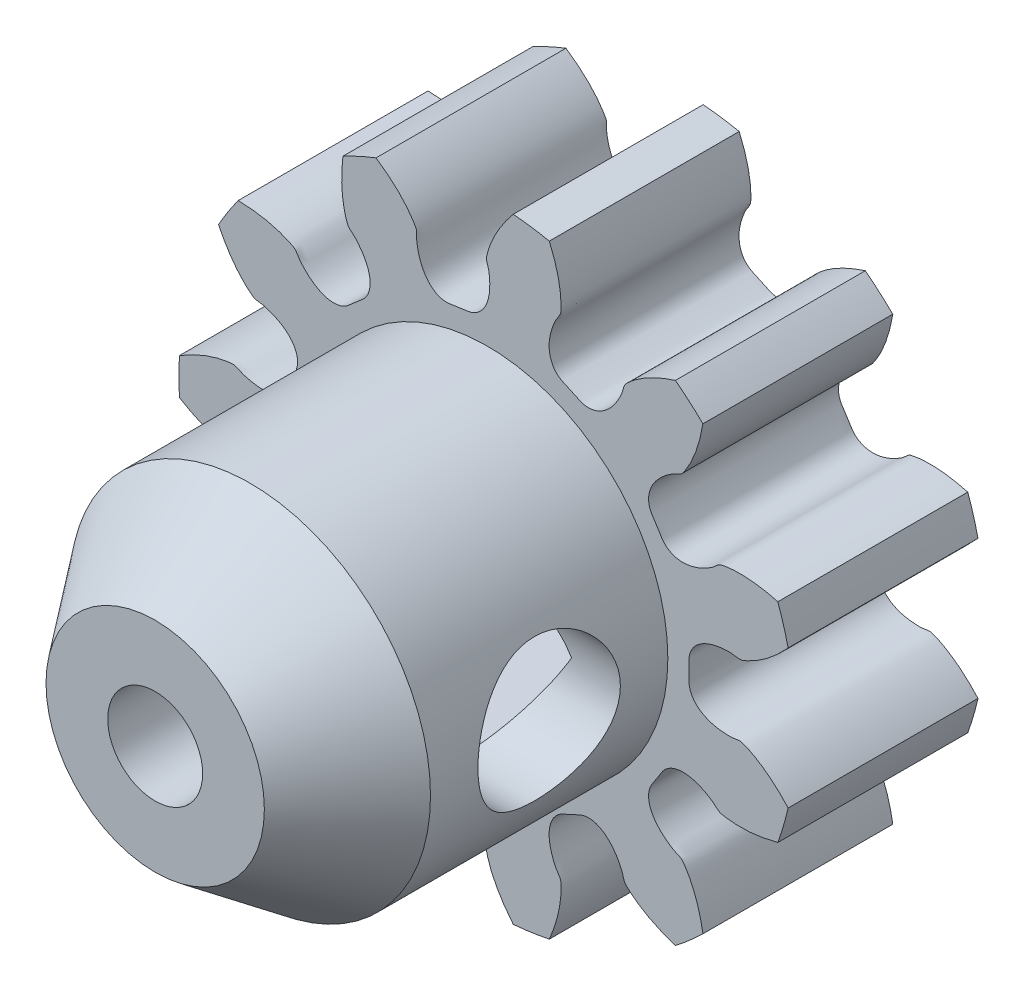
SolidWorks part; units mm, degrees
ref_plane "Front Plane" through (0, 0, 0) normal (0, 0, 1) x (1, 0, 0)
ref_plane "Top Plane" through (0, 0, 0) normal (0, 1, 0) x (1, 0, 0)
ref_plane "Right Plane" through (0, 0, 0) normal (1, 0, 0) x (0, 0, -1)
ref_axis "Axis1" through (0, 0, 55) along (0, 0, -1)
sketch "SketchRevolveSpurPinion" plane through (0, 0, 0) normal (1, 0, 0) x (0, 0, -1)
  line L0 (0, 0) -> (1, 0) construction
  line L1 (-2, 0) -> (-2, 6.5)
  line L2 (-2, 6.5) -> (2, 6.5)
  line L3 (2, 6.5) -> (2, 0)
  line L4 (2, 0) -> (-2, 0)
  dimension "Side1" = 2
  dimension "OutsideRadius" = 6.5
  dimension "Side2" = 2
revolve "SpurPinion" add sketch "SketchRevolveSpurPinion" angle 360 about L0
sketch "SketchToothSpurPinion" plane through (0, 0, 0) normal (0, 0, 1) x (1, 0, 0)
  arc A0 (6.3745, 1.5059) -> (6.3745, -1.5059) centre (0, 0) cw
  spline S0 degree 3 poles (6.3745, -1.5059) (6.3177, -1.4407) (6.2314, -1.3483) (6.113, -1.2348) (6.029, -1.1597) (5.9475, -1.092) (5.8691, -1.0315) (5.7941, -0.9778) (5.7229, -0.9306) (5.6559, -0.8896) (5.5935, -0.8543) (5.5358, -0.8245) (5.4834, -0.7993) (5.4233, -0.7745) (5.313, -0.7233) (5.1908, -0.7688) (5.0835, -0.7666) (5.0313, -0.7657) (4.9804, -0.7627) (4.9307, -0.7582) (4.8824, -0.7521) (4.8354, -0.7444) (4.7897, -0.7351) (4.7453, -0.7242) (4.7022, -0.7118) (4.6604, -0.6976) (4.6198, -0.6818) (4.5806, -0.6643) (4.5426, -0.6448) (4.506, -0.6234) (4.4707, -0.5999) (4.4368, -0.5741) (4.4045, -0.5458) (4.3739, -0.5148) (4.3453, -0.4808) (4.3191, -0.4436) (4.2958, -0.4032) (4.2761, -0.3595) (4.2606, -0.3128) (4.25, -0.2636) (4.2458, -0.218) (4.2449, -0.13) (4.2528, 0) (4.2449, 0.13) (4.2458, 0.218) (4.25, 0.2636) (4.2606, 0.3128) (4.2761, 0.3595) (4.2958, 0.4032) (4.3191, 0.4436) (4.3453, 0.4808) (4.3739, 0.5148) (4.4045, 0.5458) (4.4368, 0.5741) (4.4707, 0.5999) (4.506, 0.6234) (4.5426, 0.6448) (4.5806, 0.6643) (4.6198, 0.6818) (4.6604, 0.6976) (4.7022, 0.7118) (4.7453, 0.7242) (4.7897, 0.7351) (4.8354, 0.7444) (4.8824, 0.7521) (4.9307, 0.7582) (4.9804, 0.7627) (5.0313, 0.7657) (5.0835, 0.7666) (5.1908, 0.7688) (5.313, 0.7233) (5.4233, 0.7745) (5.4834, 0.7993) (5.5358, 0.8245) (5.5935, 0.8543) (5.6559, 0.8896) (5.7229, 0.9306) (5.7941, 0.9778) (5.8691, 1.0315) (5.9475, 1.092) (6.029, 1.1597) (6.113, 1.2348) (6.2314, 1.3483) (6.3177, 1.4407) (6.3745, 1.5059) knots 0 0 0 0 0.045121 0.0659 0.085492 0.103896 0.121113 0.137143 0.151985 0.16564 0.178107 0.189388 0.19948 0.208386 0.223471 0.261154 0.27045 0.279528 0.288392 0.297051 0.305514 0.313791 0.321893 0.329833 0.337626 0.345288 0.35284 0.360302 0.3677 0.375062 0.382419 0.389805 0.397257 0.404815 0.412518 0.420401 0.428492 0.43681 0.445354 0.454105 0.463019 0.469161 0.5 0.530839 0.536981 0.545895 0.554646 0.56319 0.571508 0.579599 0.587482 0.595185 0.602743 0.610195 0.617581 0.624938 0.6323 0.639698 0.64716 0.654712 0.662374 0.670167 0.678107 0.686209 0.694486 0.702949 0.711608 0.720472 0.72955 0.738846 0.776529 0.791614 0.80052 0.810612 0.821893 0.83436 0.848015 0.862857 0.878887 0.896104 0.914508 0.9341 0.954879 1 1 1 1
extrude "ToothExtrudeCutSpurPinion" cut sketch "SketchToothSpurPinion" against normal blind 2 and the other way blind 2
pattern_circular "PatternSpurPinion" count 11 every 32.727 about axis through (0, 0, 55) along (0, 0, -1) of "ToothExtrudeCutSpurPinion"
sketch "AuxiliarySketchSpurPinion" plane through (0, 0, 0) normal (0, 0, 1) x (1, 0, 0)
  circle A0 centre (0, 0) radius 5.5 construction
  circle A1 centre (0, 0) radius 5.3248 construction
  circle A2 centre (0, 0) radius 5.9795 construction
  circle A3 centre (0, 0) radius 6.5 construction
  circle A4 centre (0, 0) radius 4.2492 construction
  dimension "PitchDiameter" = 11
  dimension "BaseDiameter" = 10.6496
  dimension "FormDiameter" = 11.9589
  dimension "MajorDiameter" = 13
  dimension "MinorDiameter" = 8.4984
sketch "Sketch1" plane through (0, 0, 2) normal (0, 0, 1) x (1, 0, 0)
  circle A1 centre (0, 0) radius 3.8
  point P4 (0, 0)
  point P6 (0, 0)
  dimension "D1" = 7.6
extrude "Boss-Extrude1" add sketch "Sketch1" along normal blind 7
chamfer "Chamfer1" distance 2 distance2 1.5 1 edges at (3.8, 0, 9) first distance on face at (3.8, 0, 9)
sketch "Sketch3" plane through (0, 0, 0) normal (1, 0, 0) x (0, 0, -1)
  line L0 (-9, 0) -> (0, 0) construction
  line L1 (-9, 2.3) -> (-9, -2.3) construction
  line L2 (2, -1.46) -> (2, 1.46) construction
  circle A0 centre (-4.5, 0) radius 1.5
  dimension "D1" = 3
  dimension "D2" = 6.5
sketch "Sketch4" plane through (0, 0, -2) normal (0, 0, -1) x (-1, 0, 0)
  line L1 (2.7713, 0) -> (1.3856, 2.4)
  line L2 (1.3856, 2.4) -> (-1.3856, 2.4)
  line L3 (-1.3856, 2.4) -> (-2.7713, 0)
  line L4 (-2.7713, 0) -> (-1.3856, -2.4)
  line L5 (-1.3856, -2.4) -> (1.3856, -2.4)
  line L6 (1.3856, -2.4) -> (2.7713, 0)
  circle A0 centre (0, 0) radius 2.4 construction
  dimension "D1" = 4.8
extrude "Cut-Extrude1" cut sketch "Sketch4" against normal blind 9
extrude "Cut-Extrude2" cut sketch "Sketch3" along normal blind 9
sketch "Sketch5" plane through (0, 0, 9) normal (0, 0, 1) x (1, 0, 0)
  circle A0 centre (0, 0) radius 1
  dimension "D1" = 2
extrude "Cut-Extrude3" cut sketch "Sketch5" against normal blind 2
